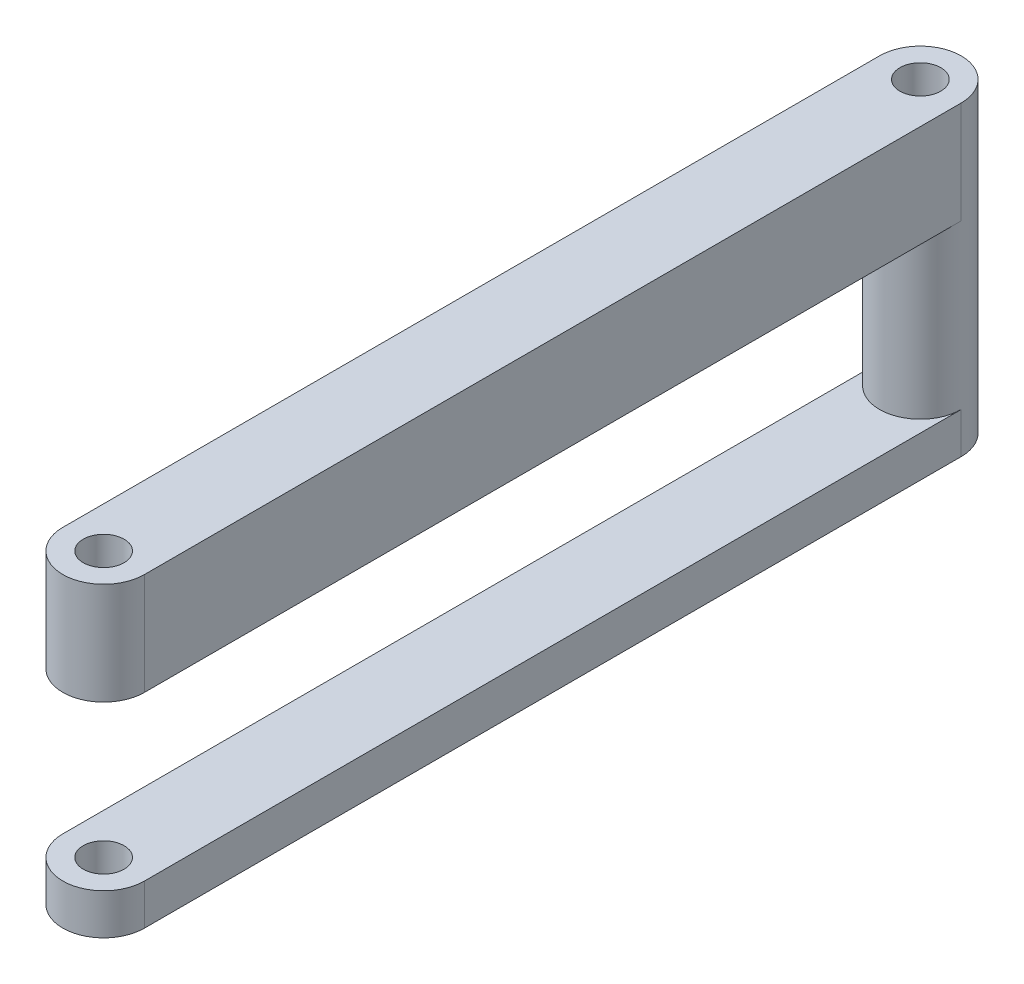
SolidWorks part; units mm, degrees
material "ABS"
ref_plane "Front Plane" through (0, 0, 0) normal (0, 0, 1) x (1, 0, 0)
ref_plane "Top Plane" through (0, 0, 0) normal (0, 1, 0) x (1, 0, 0)
ref_plane "Right Plane" through (0, 0, 0) normal (1, 0, 0) x (0, 0, -1)
sketch "Sketch1" plane through (0, 0, 0) normal (0, 1, 0) x (1, 0, 0)
  line L0 (0, 0) -> (0, -40) construction
  line L1 (2, 0) -> (2, -40)
  line L2 (-2, 0) -> (-2, -40)
  arc A0 (2, 0) -> (-2, 0) centre (0, 0) ccw
  arc A1 (-2, -40) -> (2, -40) centre (0, -40) ccw
  point P3 (0, -20)
  dimension "D2" = 2
  dimension "D1" = 40
extrude "Boss-Extrude1" add sketch "Sketch1" along normal blind 2 contours L1 A1 L2 A0
sketch "Sketch2" plane through (0, 2, 0) normal (0, 1, 0) x (1, 0, 0)
  circle A0 centre (0, 0) radius 2
  dimension "D1" = 4
extrude "Boss-Extrude2" add sketch "Sketch2" along normal blind 12
extrude "Boss-Extrude3" add sketch "Sketch1<3>" along normal blind 5 from offset 10
sketch "Sketch1<3>" plane through (0, 0, 0) normal (0, 1, 0) x (1, 0, 0) same geometry as "Sketch1"
hole_wizard "Ø2.0mm Clearance Dowel Hole1" positions "Sketch3" profile "Sketch4" hole size "Ø2.0" standard "ANSI Metric" end condition through all
sketch "Sketch3" plane through (0, 15, 0) normal (0, 1, 0) x (1, 0, 0)
  point P0 (0, 0)
  point P3 (0, -40)
sketch "Sketch4" plane through (0, 15, 0) normal (1, 0, 0) x (0, 0, 1)
  line L0 (0, 0) -> (0, 15)
  line L1 (0, 15) -> (1, 15)
  line L2 (1, 15) -> (1, 0)
  line L5 (1, 0) -> (0, 0)
  line L11 (0, -6.35) -> (0, 107.95) construction
  dimension "Thru Hole Dia." = 2
  dimension "Thru Hole Depth" = 15
